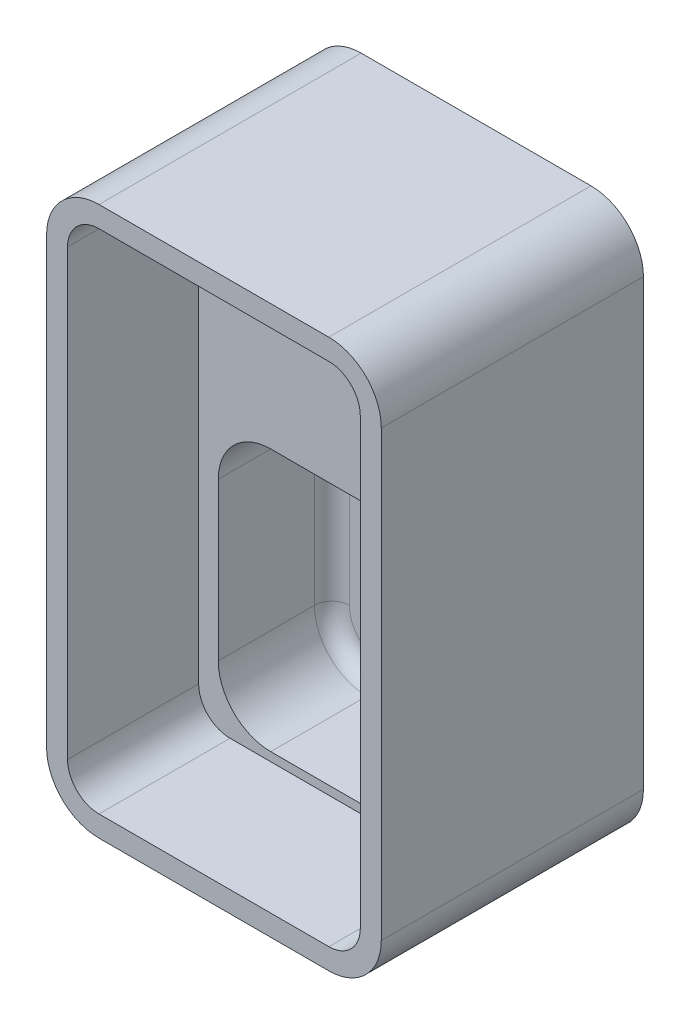
SolidWorks part; units mm, degrees
ref_plane "Front Plane" through (0, 0, 0) normal (0, 0, 1) x (1, 0, 0)
ref_plane "Top Plane" through (0, 0, 0) normal (0, 1, 0) x (1, 0, 0)
ref_plane "Right Plane" through (0, 0, 0) normal (1, 0, 0) x (0, 0, -1)
sketch "Sketch1" plane through (0, 0, 0) normal (0, 0, 1) x (1, 0, 0)
  line L1 (-14.5, 15) -> (14.5, 15)
  line L2 (-14.5, 15) -> (-14.5, -15)
  line L3 (-14.5, -15) -> (14.5, -15)
  line L4 (14.5, 15) -> (14.5, -15)
  line L5 (-14.5, 15) -> (14.5, -15) construction
  line L6 (-14.5, -15) -> (14.5, 15) construction
  line L7 (-16.75, -16) -> (16.75, -16)
  line L8 (-16.75, -16) -> (-16.75, 42)
  line L9 (-16.75, 42) -> (16.75, 42)
  line L10 (16.75, -16) -> (16.75, 42)
  line L11 (-19.15, 44.4) -> (19.15, 44.4)
  line L12 (-19.15, 44.4) -> (-19.15, -18.4)
  line L13 (-19.15, -18.4) -> (19.15, -18.4)
  line L14 (19.15, 44.4) -> (19.15, -18.4)
  circle A0 centre (0, 0) radius 7
  point P0 (0, 0)
  dimension "D11" = 14
  dimension "D1" = 30
  dimension "D2" = 29
  dimension "D3" = 16
  dimension "D4" = 58
  dimension "D5" = 33.5
  dimension "D6" = 16.75
  dimension "D7" = 2.4
  dimension "D8" = 2.4
  dimension "D9" = 2.4
  dimension "D10" = 2.4
extrude "Boss-Extrude1" add sketch "Sketch1" along normal blind 2 contours L7 L10 L9 L8 L1 L4 L3 L2 | L14 L11 L12 L13 L10 L7 L8 L9 | L4 L1 L2 L3 A0 region at (0, 14.5827, 0) region at (0, 23.5405, 0) region at (0, 43.6644, 0)
extrude "Boss-Extrude2" add sketch "Sketch1<3>" along normal blind 13 from surface contours L7 L10 L9 L8 L1 L4 L3 L2 | L14 L11 L12 L13 L10 L7 L8 L9 region at (0, 23.5405, 0) region at (0, 43.6644, 0) starting at face at (0, 13, 2)
sketch "Sketch1<3>" plane through (0, 0, 0) normal (0, 0, 1) x (1, 0, 0) same geometry as "Sketch1"
extrude "Boss-Extrude3" add sketch "Sketch1<4>" along normal blind 15 from surface contours L14 L11 L12 L13 L10 L7 L8 L9 region at (0, 43.6644, 0) starting at face at (0, 0, 15)
sketch "Sketch1<4>" plane through (0, 0, 0) normal (0, 0, 1) x (1, 0, 0) same geometry as "Sketch1"
fillet "Fillet1" radius 3.6 4 edges at (-16.75, -16, 22.5) (16.75, -16, 22.5) (-16.75, 42, 22.5) (16.75, 42, 22.5)
fillet "Fillet2" radius 6 8 edges at (-14.5, -15, 8.5) (-14.5, 15, 8.5) (14.5, -15, 8.5) (14.5, 15, 8.5) (19.15, -18.4, 15) (-19.15, -18.4, 15) (-19.15, 44.4, 15) (19.15, 44.4, 15)
fillet "Fillet3" radius 2 8 edges at (12.7426, 13.2426, 2) (14.5, 0, 2) (12.7426, -13.2426, 2) (0, -15, 2) (-12.7426, -13.2426, 2) (-14.5, 0, 2) (-12.7426, 13.2426, 2) (0, 15, 2)
